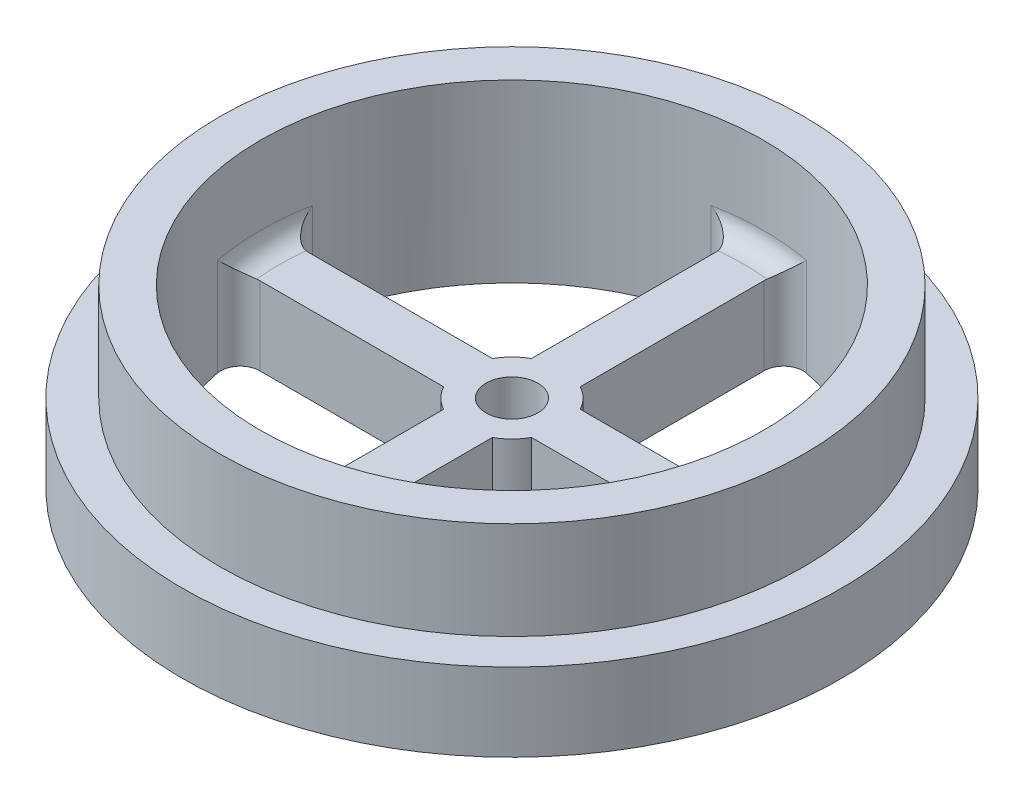
SolidWorks part; units mm, degrees
ref_plane "Front Plane" through (0, 0, 0) normal (0, 0, 1) x (1, 0, 0)
ref_plane "Top Plane" through (0, 0, 0) normal (0, 1, 0) x (1, 0, 0)
ref_plane "Right Plane" through (0, 0, 0) normal (1, 0, 0) x (0, 0, -1)
sketch "Sketch1" plane through (0, 0, 0) normal (0, 0, 1) x (1, 0, 0)
  line L0 (0, 0) -> (42.8625, 0) construction
  line L1 (42.8625, 0) -> (42.8625, 10.16)
  line L2 (42.8625, 10.16) -> (37.9984, 10.16)
  line L3 (37.9984, 10.16) -> (37.9984, 22.86)
  line L4 (37.9984, 22.86) -> (0, 22.86) construction
  line L5 (0, 22.86) -> (0, 0) construction
  line L6 (32.7025, 22.86) -> (32.7025, 0)
  line L7 (42.8625, 0) -> (32.7025, 0)
  line L8 (37.9984, 22.86) -> (32.7025, 22.86)
  dimension "D1" = 42.8625
  dimension "D2" = 10.16
  dimension "D3" = 37.9984
  dimension "D4" = 22.86
  dimension "D5" = 32.7025
revolve "Revolve2" add sketch "Sketch1" angle 360 about L5
sketch "Sketch2" plane through (0, 0, 0) normal (0, -1, 0) x (1, 0, 0)
  line L0 (0, 0) -> (0, 54.3276) construction
  line L1 (0, 0) -> (-57.2898, 0) construction
  line L2 (-3.175, 5.7182) -> (-3.175, 32.548)
  line L3 (-5.7182, 3.175) -> (-32.548, 3.175)
  line L4 (3.175, 5.7182) -> (3.175, 32.548)
  line L5 (5.7182, 3.175) -> (32.548, 3.175)
  line L6 (5.7182, -3.175) -> (32.548, -3.175)
  line L7 (3.175, -5.7182) -> (3.175, -32.548)
  line L8 (-3.175, -5.7182) -> (-3.175, -32.548)
  line L9 (-5.7182, -3.175) -> (-32.548, -3.175)
  arc A2 (-3.175, 32.548) -> (-32.548, 3.175) centre (0, 0) ccw construction
  circle A3 centre (0, 0) radius 42.8625
  circle A4 centre (0, 0) radius 42.8625
  arc A5 (-3.175, 5.7182) -> (-5.7182, 3.175) centre (0, 0) ccw
  circle A6 centre (0, 0) radius 32.7025 construction
  circle A7 centre (0, 0) radius 3.3655
  arc A8 (32.548, 3.175) -> (3.175, 32.548) centre (0, 0) ccw construction
  arc A9 (5.7182, 3.175) -> (3.175, 5.7182) centre (0, 0) ccw
  arc A10 (3.175, -32.548) -> (32.548, -3.175) centre (0, 0) ccw construction
  arc A11 (3.175, -5.7182) -> (5.7182, -3.175) centre (0, 0) ccw
  arc A12 (-32.548, -3.175) -> (-3.175, -32.548) centre (0, 0) ccw construction
  arc A13 (-5.7182, -3.175) -> (-3.175, -5.7182) centre (0, 0) ccw
  circle A14 centre (0, 0) radius 32.7025
  point P34 (0, 0)
  circle M14 centre (0, 0) radius 32.7025
  dimension "D4" = 0
  dimension "D5" = 6.731
  dimension "D6" = 3.175
  dimension "D1" = 3.175
  dimension "D2" = 3.175
  dimension "D3" = 0
  dimension "D7" = 4
extrude "Boss-Extrude1" add sketch "Sketch2" against normal blind 10.16 contours L9 A13 L8 L7 A11 L6 L5 A9 L4 L2 A5 L3 A7 M14 region at (-2.25, 0, 19.1331)
fillet "Fillet1" radius 2.54 12 edges at (-32.7025, 10.16, 0) (-32.548, 5.08, 3.175) (3.175, 5.08, -32.548) (3.175, 5.08, 32.548) (0, 10.16, 32.7025) (-32.548, 5.08, -3.175) (0, 10.16, -32.7025) (-3.175, 5.08, -32.548) (-3.175, 5.08, 32.548) (32.548, 5.08, -3.175) (32.7025, 10.16, 0) (32.548, 5.08, 3.175)
